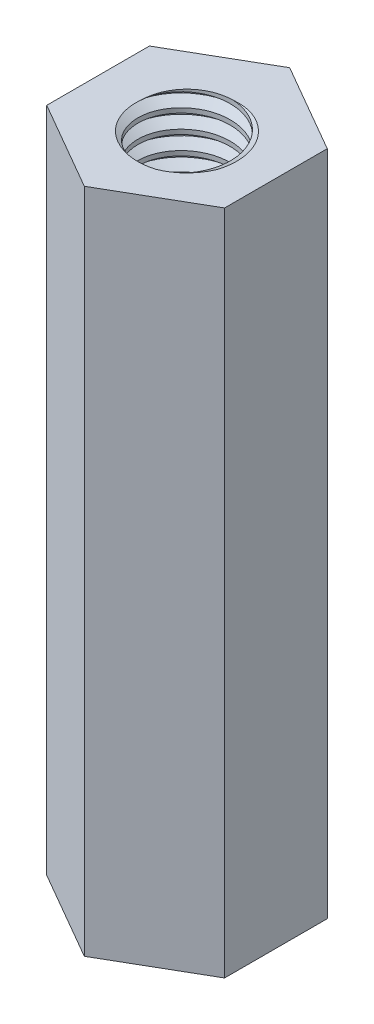
SolidWorks part; units mm, degrees
ref_plane "Front Plane" through (0, 0, 0) normal (0, 0, 1) x (1, 0, 0)
ref_plane "Top Plane" through (0, 0, 0) normal (0, 1, 0) x (1, 0, 0)
ref_plane "Right Plane" through (0, 0, 0) normal (1, 0, 0) x (0, 0, -1)
sketch "Sketch1" plane through (0, 0, 0) normal (0, 1, 0) x (1, 0, 0)
  line L1 (2.4, 1.3856) -> (0, 2.7713)
  line L2 (0, 2.7713) -> (-2.4, 1.3856)
  line L3 (-2.4, 1.3856) -> (-2.4, -1.3856)
  line L4 (-2.4, -1.3856) -> (0, -2.7713)
  line L5 (0, -2.7713) -> (2.4, -1.3856)
  line L6 (2.4, -1.3856) -> (2.4, 1.3856)
  circle A0 centre (0, 0) radius 2.4 construction
  circle A1 centre (0, 0) radius 1.25
  dimension "D1" = 4.8
  dimension "D2" = 2.5
extrude "Boss-Extrude1" add sketch "Sketch1" along normal mid plane 18
thread "Thread1" pitch 0.5 method cut profile "Thread Profile1" start angle 0, offset 2, length 22, pitch 0.5, diameter 2.5
ref_plane "Plane1" through (-1.25, 11, 0) normal (0, 0, 1) x (-1, 0, 0)
sketch "Thread Profile1" plane through (-1.25, 11, 0) normal (0, 0, 1) x (-1, 0, 0)
  line L0 (0, 0) -> (0, 0.5) construction
  line L1 (0, 0) -> (0.2706, 0.1562)
  line L2 (0.2706, 0.1562) -> (0.2706, 0.2187)
  line L3 (0.2706, 0.2187) -> (0, 0.375)
  line L4 (0.2706, 0.1875) -> (0, 0.1875) construction
  line L11 (0, 0) -> (0, 0.375)
  point P2 (0, 0)
  dimension "Pitch" = 0.5
  dimension "Profile_Angle" = 60
  dimension "Profile_Land" = 0.0625
  dimension "Profile_Height" = 0.2706
sketch "Sketch3" plane through (0, 0, 0) normal (0, 1, 0) x (1, 0, 0)
  line L6 (2.4, -1.3856) -> (2.4, 1.3856)
  line L7 (2.4, 1.3856) -> (0, 2.7713)
  line L8 (0, 2.7713) -> (-2.4, 1.3856)
  line L9 (-2.4, 1.3856) -> (-2.4, -1.3856)
  line L10 (-2.4, -1.3856) -> (0, -2.7713)
  line L11 (0, -2.7713) -> (2.4, -1.3856)
  line L12 (2.4, -1.3856) -> (2.4, 1.3856)
  line L13 (2.4, 1.3856) -> (0, 2.7713)
  line L14 (0, 2.7713) -> (-2.4, 1.3856)
  line L15 (-2.4, 1.3856) -> (-2.4, -1.3856)
  line L16 (-2.4, -1.3856) -> (0, -2.7713)
  line L17 (0, -2.7713) -> (2.4, -1.3856)
  dimension "D1" = 0
extrude "Boss-Extrude2" add sketch "Sketch3" along normal mid plane 8
